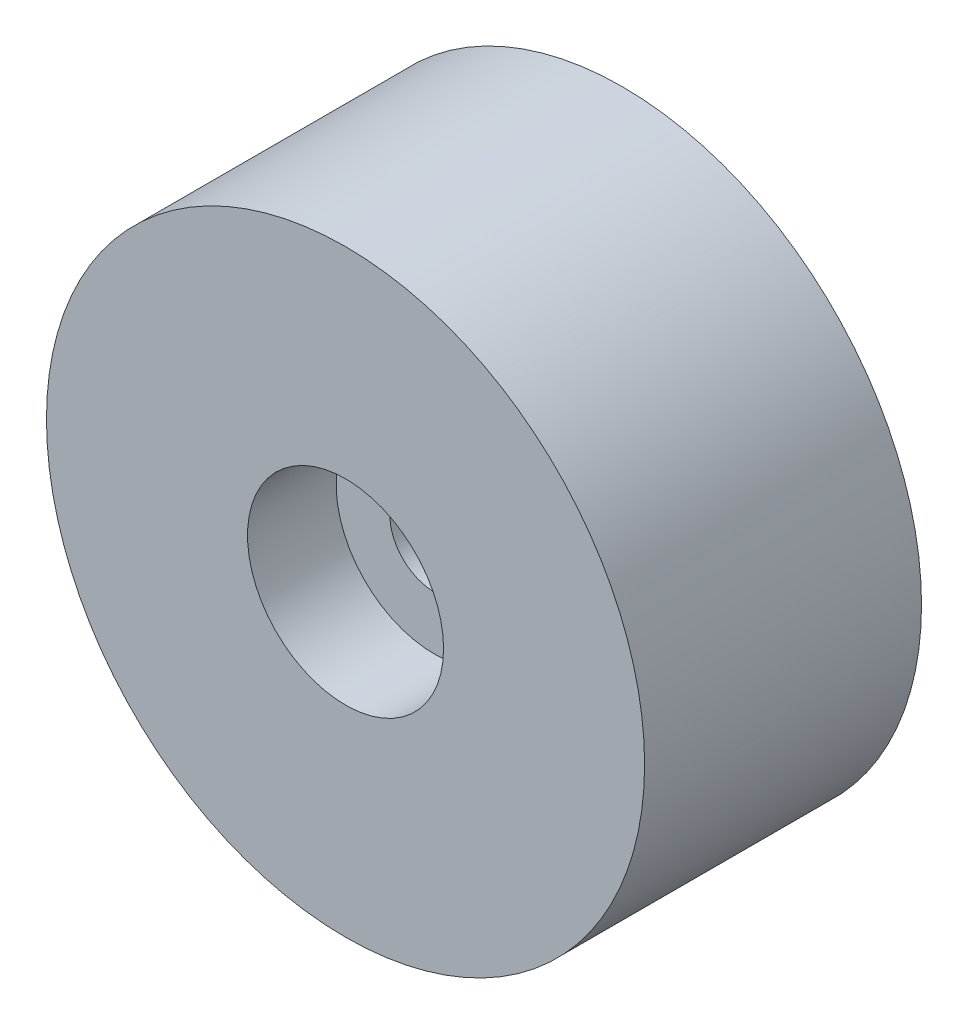
SolidWorks part; units mm, degrees
ref_plane "Front" through (0, 0, 0) normal (0, 0, 1) x (1, 0, 0)
ref_plane "Top" through (0, 0, 0) normal (0, 1, 0) x (1, 0, 0)
ref_plane "Right" through (0, 0, 0) normal (1, 0, 0) x (0, 0, -1)
sketch "Esquisse1" plane through (0, 0, 0) normal (0, 0, 1) x (1, 0, 0)
  circle A0 centre (0, 0) radius 27
  dimension "D1" = 54
extrude "Boss.-Extru.1" add sketch "Esquisse1" along normal blind 25
sketch "Esquisse2" plane through (0, 0, 25) normal (0, 0, 1) x (1, 0, 0)
  circle A0 centre (0, 0) radius 8.85
  dimension "D1" = 17.7
extrude "Enlèv. mat.-Extru.1" cut sketch "Esquisse2" against normal blind 8
sketch "Esquisse3" plane through (0, 0, 17) normal (0, 0, 1) x (1, 0, 0)
  circle A0 centre (0, 0) radius 4
  dimension "D1" = 8
extrude "Enlèv. mat.-Extru.2" cut sketch "Esquisse3" against normal through all
